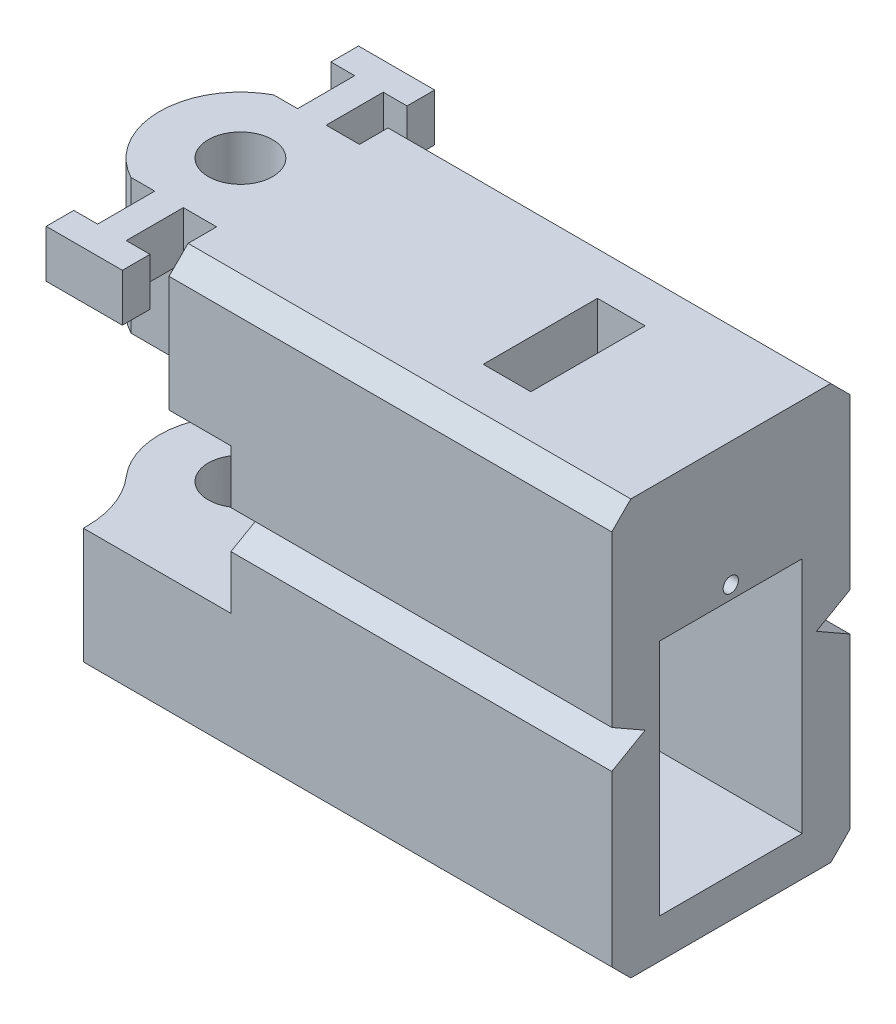
SolidWorks part; units mm, degrees
ref_plane "Front Plane" through (0, 0, 0) normal (0, 0, 1) x (1, 0, 0)
ref_plane "Top Plane" through (0, 0, 0) normal (0, 1, 0) x (1, 0, 0)
ref_plane "Right Plane" through (0, 0, 0) normal (1, 0, 0) x (0, 0, -1)
sketch "Sketch1" plane through (0, 0, 0) normal (1, 0, 0) x (0, 0, -1)
  line L0 (3.5, 21.787) -> (21.5, 21.787) construction
  line L1 (0, 0) -> (25, 0)
  line L2 (0, 0) -> (0, 19.787)
  line L3 (0, 43.574) -> (25, 43.574)
  line L4 (25, 0) -> (25, 19.787)
  line L5 (0, 23.787) -> (3.5, 21.787)
  line L6 (0, 19.787) -> (3.5, 21.787)
  line L7 (12.5, 43.574) -> (12.5, 0) construction
  line L8 (25, 23.787) -> (21.5, 21.787)
  line L9 (25, 19.787) -> (21.5, 21.787)
  line L10 (0, 23.787) -> (0, 43.574)
  line L11 (25, 23.787) -> (25, 43.574)
  point P6 (12.5, 21.787)
  dimension "D1" = 43.574
  dimension "D2" = 25
  dimension "D3" = 4
  dimension "D4" = 18
extrude "Boss-Extrude1" add sketch "Sketch1" along normal blind 55.5
chamfer "Chamfer1" distance 2 angle 45 4 edges at (27.75, 43.574, -25) (27.75, 43.574, 0) (27.75, 0, -25) (27.75, 0, 0)
sketch "Sketch4" plane through (0, 43.574, 0) normal (0, 1, 0) x (1, 0, 0)
  line L5 (0, 23) -> (0, 2) construction
  line L11 (0, 28.9) -> (8, 28.9)
  line L30 (0, 28.9) -> (0, -3.9)
  line L31 (0, -3.9) -> (8, -3.9)
  line L32 (8, 28.9) -> (8, -3.9)
  point P6 (0, 12.5)
  dimension "D1" = 32.8
  dimension "D2" = 8
extrude "Boss-Extrude2" add sketch "Sketch4" against normal blind 5
sketch "Sketch7" plane through (0, 43.574, 0) normal (0, 1, 0) x (1, 0, 0)
  line L0 (4, 28.9) -> (4, -3.9) construction
  line L1 (8, 28.9) -> (0, 28.9) construction
  line L2 (0, -3.9) -> (8, -3.9) construction
  line L3 (55.5, 12.5) -> (0, 12.5) construction
  line L4 (55.5, 23) -> (55.5, 2) construction
  line L5 (0, 28.9) -> (0, -3.9) construction
  line L6 (9, 5) -> (5.5, 5)
  line L7 (9, 26) -> (5.5, 26)
  line L8 (9, 26) -> (9, 20)
  line L9 (9, 20) -> (5.5, 20)
  line L10 (5.5, 26) -> (5.5, 20)
  line L11 (5.5, 23) -> (5.5, 12.5) construction
  line L12 (5.5, -1) -> (5.5, 5)
  line L13 (9, -1) -> (5.5, -1)
  line L14 (9, -1) -> (9, 5)
  line L15 (-1, -1) -> (-1, 5)
  line L16 (-1, -1) -> (2.5, -1)
  line L17 (2.5, -1) -> (2.5, 5)
  line L18 (-1, 5) -> (2.5, 5)
  line L19 (-1, 20) -> (2.5, 20)
  line L20 (2.5, 26) -> (2.5, 20)
  line L21 (-1, 26) -> (2.5, 26)
  line L22 (-1, 26) -> (-1, 20)
  dimension "D1" = 6
  dimension "D2" = 1.5
  dimension "D3" = 10.5
  dimension "D4" = 3.5
extrude "Cut-Extrude5" cut sketch "Sketch7" against normal blind 10
sketch "Sketch5" plane through (0, 43.574, 0) normal (0, 1, 0) x (1, 0, 0)
  line L0 (4, 28.9) -> (4, -3.9) construction
  line L1 (8, 28.9) -> (0, 28.9) construction
  line L2 (0, -3.9) -> (8, -3.9) construction
  circle A0 centre (4, 12.5) radius 1 construction
  circle A1 centre (4, 12.5) radius 3.375
  dimension "D1" = 2
  dimension "D2" = 6.75
extrude "Cut-Extrude3" cut sketch "Sketch5" against normal through all contours A1
ref_plane "Plane1" through (0, 21.787, 0) normal (0, -1, 0) x (-1, 0, 0)
sketch "Sketch6" plane through (0, 21.787, 0) normal (0, -1, 0) x (-1, 0, 0)
  line L6 (-4, 30) -> (4.5, 30)
  line L7 (4.5, 30) -> (4.5, -5)
  line L9 (4.5, -5) -> (-4, -5)
  line L10 (-15.5, -5) -> (-15.5, 30)
  line L11 (-15.5, 30) -> (-4, 30)
  line L12 (-15.5, -5) -> (-4, -5)
  circle A1 centre (-4, 12.5) radius 3.375 construction
  circle A5 centre (-4, 12.5) radius 3.375
  dimension "D1" = 15.5
  dimension "D2" = 20
  dimension "D3" = 35
  dimension "D4" = 17.5
extrude "Cut-Extrude4" cut sketch "Sketch6" against normal mid plane 15.24
sketch "Sketch8" plane through (0, 29.407, 0) normal (0, -1, 0) x (1, 0, 0)
  line L0 (9, 0) -> (9, -5) construction
  line L9 (9, -20) -> (9, -25) construction
  line L10 (9, 0) -> (9, -5)
  line L11 (9, -20) -> (9, -25)
  line L13 (9, -20) -> (0, -20)
  line L14 (9, -20) -> (9, -25)
  line L15 (9, -25) -> (0, -25)
  line L16 (0, -20) -> (0, -25)
  line L17 (9, -5) -> (0, -5)
  line L18 (9, -5) -> (9, 0)
  line L19 (9, 0) -> (0, 0)
  line L20 (0, -5) -> (0, 0)
  line M8 (15.5, 0) -> (0, 0)
  line M11 (0, 0) -> (0, -25)
  line M14 (0, -25) -> (15.5, -25)
extrude "Cut-Extrude6" cut sketch "Sketch8" against normal up to surface (9.167 mm away) contours L11 L13 M11 M14 | L17 L10 M8 M11 region at (4.5, 29.407, -22.5) region at (4.5, 29.407, -2.5) up to face at (4, 38.574, 1.475)
sketch "Sketch9" plane through (0, 43.574, 0) normal (0, 1, 0) x (1, 0, 0)
  line L0 (0, 20) -> (0, 5)
  arc A0 (0, 20) -> (0, 5) centre (4, 12.5) ccw
extrude "Boss-Extrude3" add sketch "Sketch9" against normal up to surface (14.167 mm away) up to face at (8.375, 29.407, -12.5)
extrude "Boss-Extrude4" add sketch "Sketch9<2>" along direction (0, 1, 0) on the side against the normal up to surface (43.574 mm away) from surface up to face at (4, 0, -9.125) starting at face at (4, 14.167, -15.875)
sketch "Sketch9<2>" plane through (0, 43.574, 0) normal (0, 1, 0) x (1, 0, 0) same geometry as "Sketch9"
fillet "Fillet1" radius 10 2 edges at (0, 7.0835, -20) (0, 7.0835, -5)
sketch "Sketch10" plane through (55.5, 0, 0) normal (1, 0, 0) x (0, 0, -1)
  line L0 (21.5, 21.787) -> (3.5, 21.787) construction
  line L1 (5, 29.137) -> (20, 29.137)
  line L2 (5, 29.137) -> (5, 4.137)
  line L3 (5, 4.137) -> (20, 4.137)
  line L4 (20, 29.137) -> (20, 4.137)
  line L5 (12.5, 43.574) -> (12.5, 4.137) construction
  line L6 (23, 43.574) -> (2, 43.574) construction
  line L8 (12.5, 29.137) -> (12.5, 21.787) construction
  line L9 (5, 16.637) -> (20, 16.637) construction
  circle A0 centre (12.5, 21.787) radius 2.5 construction
  point P22 (12.5, 25.462)
  dimension "D3" = 5
  dimension "D1" = 25
  dimension "D2" = 15
  dimension "D4" = 5.15
extrude "Cut-Extrude7" cut sketch "Sketch10" against normal blind 20
sketch "Sketch11" plane through (55.5, 0, 0) normal (1, 0, 0) x (0, 0, -1)
  line L0 (12.5, 43.574) -> (12.5, 30.537) construction
  line L1 (23, 43.574) -> (2, 43.574) construction
  circle A0 centre (12.5, 30.537) radius 0.8
  dimension "D2" = 1.6
  dimension "D1" = 8.75
extrude "Cut-Extrude8" cut sketch "Sketch11" against normal blind 8
sketch "Sketch12" plane through (0, 43.574, 0) normal (0, 1, 0) x (1, 0, 0)
  line L0 (40.5, 12.5) -> (55.5, 12.5) construction
  line L1 (40.5, 18.5) -> (35.5, 18.5)
  line L2 (40.5, 18.5) -> (40.5, 6.5)
  line L3 (40.5, 6.5) -> (35.5, 6.5)
  line L4 (55.5, 5) -> (55.5, 20)
  line L5 (35.5, 5) -> (55.5, 5)
  line L6 (35.5, 20) -> (35.5, 5)
  line L7 (55.5, 20) -> (35.5, 20)
  line L8 (55.5, 5) -> (55.5, 20)
  line L9 (35.5, 5) -> (55.5, 5)
  line L10 (35.5, 20) -> (35.5, 5)
  line L11 (55.5, 20) -> (35.5, 20)
  line L12 (35.5, 18.5) -> (35.5, 6.5)
  dimension "D2" = 15
  dimension "D3" = 12
  dimension "D1" = 0
extrude "Cut-Extrude9" cut sketch "Sketch12" against normal up to surface (14.437 mm away) contours L1 L10 L3 L2 region at (38, 43.574, -12.5) up to face at (45.5, 29.137, -12.5)
